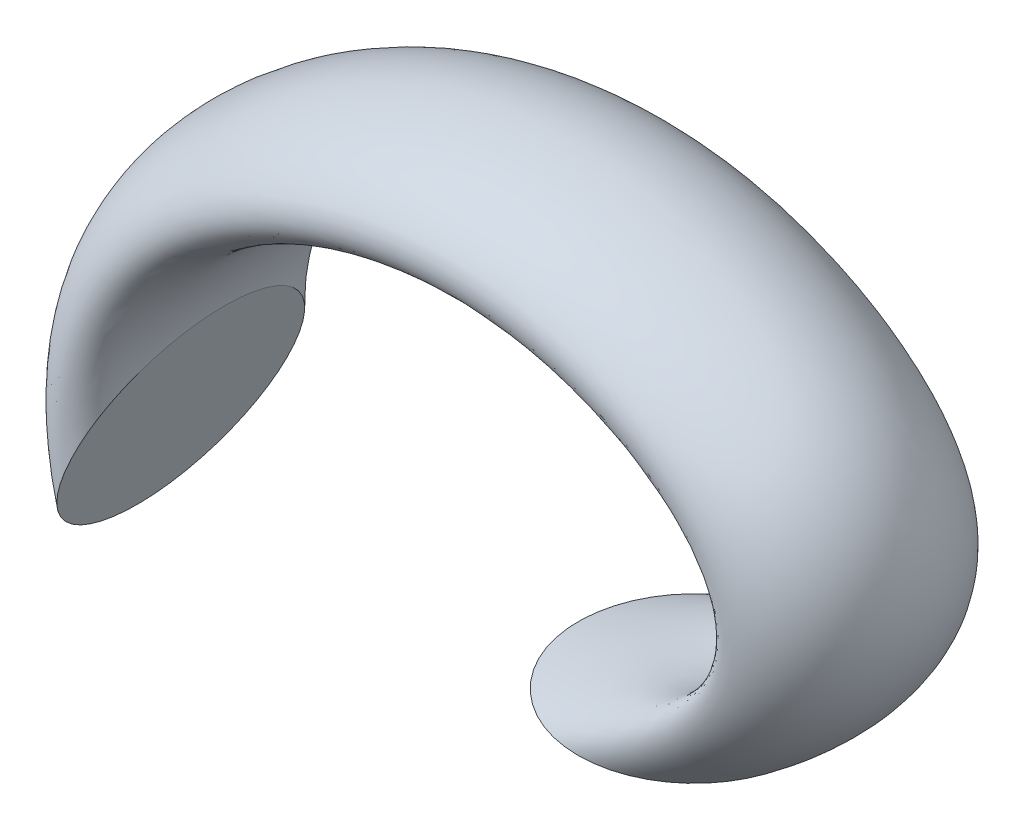
SolidWorks part; units mm, degrees
ref_plane "Front Plane" through (0, 0, 0) normal (0, 0, 1) x (1, 0, 0)
ref_plane "Top Plane" through (0, 0, 0) normal (0, 1, 0) x (1, 0, 0)
ref_plane "Right Plane" through (0, 0, 0) normal (1, 0, 0) x (0, 0, -1)
sketch "Sketch3" plane through (0, 0, 0) normal (0, 1, 0) x (1, 0, 0)
  circle A0 centre (43.7789, -68.9517) radius 52.3684
ref_plane "Plane1" through (0, 0, 68.9517) normal (0, 0, 1) x (1, 0, 0)
sketch "Sketch4" plane through (0, 0, 68.9517) normal (0, 0, 1) x (1, 0, 0)
  spline S0 degree 3 poles (43.7789, 0) (156.4501, 61.8158) (18.4285, 227.2275) (-201.3871, 108.5609) (-187.8806, -5.15) knots 0 0 0 0 0.387573 1 1 1 1
sweep "Sweep1" add profiles "Sketch3" path "Sketch4"
